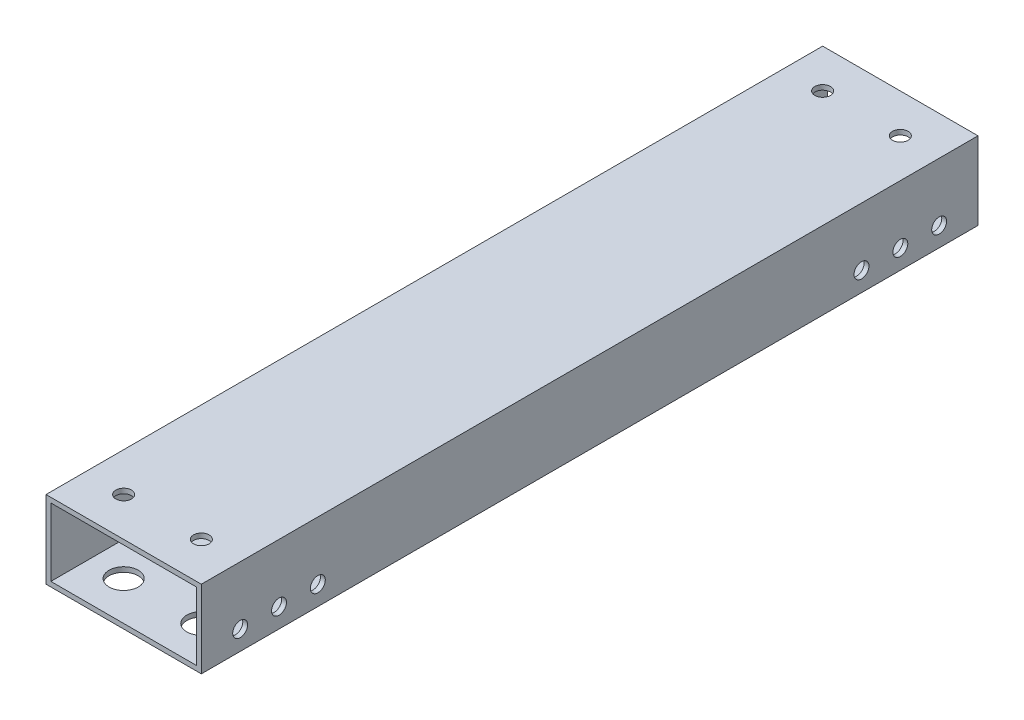
SolidWorks part; units mm, degrees
other "Markup1"
sketch "Sketch7" plane through (25.4, 12.7, -127) normal (0.9965, 0.0171, -0.0817) x (-0.082, 0.0128, -0.9966)
ref_plane "Front Plane" through (0, 0, 0) normal (0, 0, 1) x (1, 0, 0)
ref_plane "Top Plane" through (0, 0, 0) normal (0, 1, 0) x (1, 0, 0)
ref_plane "Right Plane" through (0, 0, 0) normal (1, 0, 0) x (0, 0, -1)
sketch "Sketch1" plane through (0, 0, 0) normal (0, 0, 1) x (1, 0, 0)
  line L0 (-23.8125, 11.1125) -> (23.8125, 11.1125)
  line L1 (-25.4, -12.7) -> (25.4, -12.7)
  line L2 (-25.4, -12.7) -> (-25.4, 12.7)
  line L3 (-25.4, 12.7) -> (25.4, 12.7)
  line L4 (25.4, -12.7) -> (25.4, 12.7)
  line L5 (-25.4, -12.7) -> (25.4, 12.7) construction
  line L6 (-25.4, 12.7) -> (25.4, -12.7) construction
  line L7 (23.8125, -11.1125) -> (23.8125, 11.1125)
  line L8 (-23.8125, -11.1125) -> (23.8125, -11.1125)
  line L9 (-23.8125, -11.1125) -> (-23.8125, 11.1125)
  point P0 (0, 0)
  dimension "D1" = 50.8
  dimension "D2" = 25.4
  dimension "D3" = 1.5875
extrude "Boss-Extrude1" add sketch "Sketch1" along normal mid plane 254
sketch "Sketch3" plane through (0, 12.7, 0) normal (0, 1, 0) x (1, 0, 0)
  line L0 (25.4, 127) -> (-25.4, 127) construction
  line L1 (25.4, -127) -> (-25.4, -127) construction
  line L3 (-25.4, -127) -> (-25.4, 127) construction
  line L4 (25.4, -127) -> (25.4, 127) construction
  circle A0 centre (-12.7, -114.3) radius 2.5527
  circle A1 centre (12.7, -114.3) radius 2.5527
  circle A2 centre (-12.7, 114.3) radius 2.5527
  circle A3 centre (12.7, 114.3) radius 2.5527
  dimension "D5" = 5.1054
  dimension "D1" = 12.7
  dimension "D2" = 12.7
  dimension "D3" = 12.7
  dimension "D4" = 12.7
  dimension "D6" = 25.4
  dimension "D7" = 25.4
  dimension "D8" = 12.7
  dimension "D9" = 12.7
  dimension "D10" = 12.7
  dimension "D11" = 12.7
extrude "Cut-Extrude1" cut sketch "Sketch3" against normal up to surface (1.5875 mm away) up to face at (0, 11.1125, 0)
sketch "Sketch5" plane through (0, -12.7, 0) normal (0, -1, 0) x (1, 0, 0)
  circle A0 centre (-12.7, -114.3) radius 2.5527 construction
  circle A1 centre (12.7, -114.3) radius 2.5527 construction
  circle A2 centre (12.7, 114.3) radius 2.5527 construction
  circle A3 centre (-12.7, 114.3) radius 2.5527 construction
  circle A4 centre (-12.7, -114.3) radius 2.5527
  circle A5 centre (12.7, -114.3) radius 2.5527
  circle A6 centre (12.7, 114.3) radius 2.5527
  circle A7 centre (-12.7, 114.3) radius 2.5527
  circle A8 centre (-12.7, 114.3) radius 4.7625
  circle A9 centre (12.7, 114.3) radius 4.7625
  circle A10 centre (12.7, -114.3) radius 4.7625
  circle A11 centre (-12.7, -114.3) radius 4.7625
  dimension "D1" = 9.525
extrude "Cut-Extrude2" cut sketch "Sketch5" against normal up to surface (1.5875 mm away) contours A10 A5 | A5 | A11 A4 | A4 | A6 | A9 A6 | A8 A7 | A7 region at (-12.7, -12.7, -114.3) region at (12.7, -12.7, -114.3) region at (12.7, -12.7, 114.3) region at (-12.7, -12.7, 114.3) region at (-17.3278, -12.7, 114.3) region at (8.0722, -12.7, 114.3) region at (8.0722, -12.7, -114.3) region at (-17.3278, -12.7, -114.3) up to face at (0, -11.1125, 0)
sketch "Sketch6" plane through (25.4, 0, 0) normal (1, 0, 0) x (0, 0, -1)
  line L0 (-127, -12.7) -> (-127, 12.7) construction
  line L1 (-127, -12.7) -> (127, -12.7) construction
  line L2 (0, 12.7) -> (0, -12.7) construction
  line L3 (-127, 12.7) -> (127, 12.7) construction
  circle A0 centre (-114.3, -6.35) radius 2.4384
  circle A1 centre (-101.6, -6.35) radius 2.4384
  circle A2 centre (-88.9, -6.35) radius 2.4384
  circle A3 centre (88.9, -6.35) radius 2.4384
  circle A4 centre (101.6, -6.35) radius 2.4384
  circle A5 centre (114.3, -6.35) radius 2.4384
  dimension "D1" = 4.8768
  dimension "D2" = 12.7
  dimension "D3" = 6.35
  dimension "D4" = 12.7
  dimension "D5" = 12.7
extrude "Cut-Extrude3" cut sketch "Sketch6" against normal up to surface (1.5875 mm away) contours A5 | A4 | A3 | A0 | A1 | A2 region at (25.4, -6.35, 114.3) region at (25.4, -6.35, 101.6) region at (25.4, -6.35, 88.9) region at (25.4, -6.35, -88.9) region at (25.4, -6.35, -101.6) region at (25.4, -6.35, -114.3) up to face at (23.8125, 0, 0)
